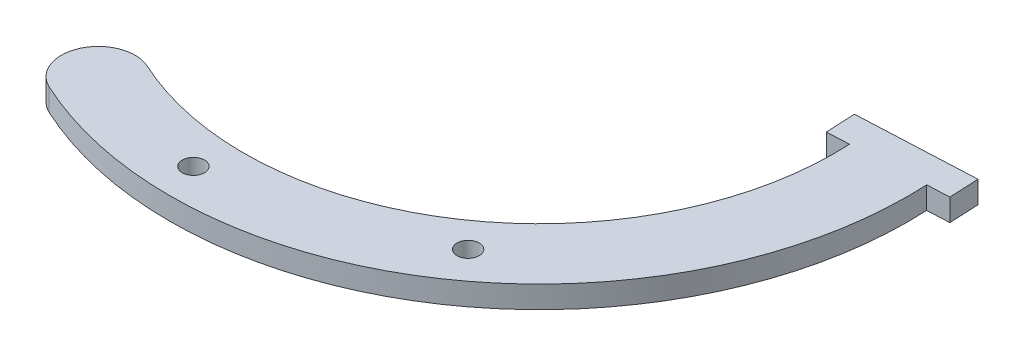
SolidWorks part; units mm, degrees
ref_plane "前视基准面" through (0, 0, 0) normal (0, 0, 1) x (1, 0, 0)
ref_plane "上视基准面" through (0, 0, 0) normal (0, 1, 0) x (1, 0, 0)
ref_plane "右视基准面" through (0, 0, 0) normal (1, 0, 0) x (0, 0, -1)
sketch "草图1" plane through (0, 0, 0) normal (0, 1, 0) x (1, 0, 0)
  line L1 (61.0237, 33.5692) -> (61.022, 33.6048)
  line L222 (71.0113, 34.0674) -> (74.0081, 34.2061)
  line L223 (74.0081, 34.2061) -> (73.8231, 38.2019)
  line L224 (73.8231, 38.2019) -> (57.8402, 37.4618)
  line L225 (57.8402, 37.4618) -> (58.0252, 33.4661)
  line L226 (58.0252, 33.4661) -> (61.022, 33.6048)
  arc A1 (4.3466, -4.7583) -> (61.0237, 33.5692) centre (21.0734, 31.5765) ccw
  circle A7 centre (47.5377, -4.5199) radius 1.5
  circle A8 centre (19.2242, -13.3908) radius 1.5
  arc A33 (4.3466, -4.7583) -> (0.1649, -13.842) centre (2.2558, -9.3001) ccw
  arc A134 (0.1649, -13.842) -> (71.0113, 34.0674) centre (21.0734, 31.5765) ccw
  point P17 (22.7627, 23.6193)
  point P31 (21.9431, -11.3711)
  point P47 (55.4539, 11.1181)
extrude "凸台-拉伸1" add sketch "草图1" along normal blind 3 contours A33 A134 L222 L223 L224 L225 L226 L1 A1 region at (61.9754, 0, -33.635)
